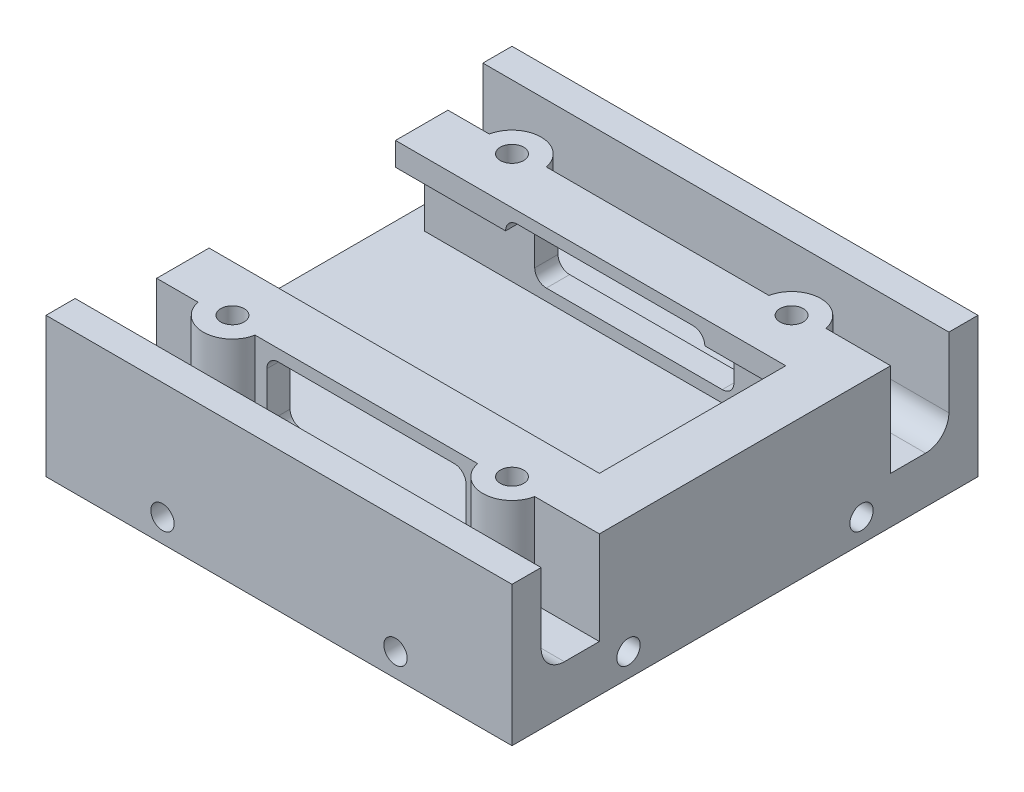
SolidWorks part; units mm, degrees
ref_plane "Front Plane" through (0, 0, 0) normal (0, 0, 1) x (1, 0, 0)
ref_plane "Top Plane" through (0, 0, 0) normal (0, 1, 0) x (1, 0, 0)
ref_plane "Right Plane" through (0, 0, 0) normal (1, 0, 0) x (0, 0, -1)
sketch "Sketch1" plane through (0, 0, 0) normal (0, 1, 0) x (1, 0, 0)
  line L1 (-20, -20) -> (20, -20)
  line L2 (-20, -20) -> (-20, 20)
  line L3 (-20, 20) -> (20, 20)
  line L4 (20, -20) -> (20, 20)
  line L5 (-20, -20) -> (20, 20) construction
  line L6 (-20, 20) -> (20, -20) construction
  point P0 (0, 0)
  dimension "D1" = 40
  dimension "D2" = 40
extrude "Boss-Extrude3" add sketch "Sketch1" along normal blind 2
sketch "Sketch5" plane through (0, 2, 0) normal (0, 1, 0) x (1, 0, 0)
  line L0 (20, -20) -> (20, 20) construction
  line L1 (-18, -10.5) -> (18, -10.5)
  line L2 (-18, -10.5) -> (-18, 10.5)
  line L3 (-18, 10.5) -> (18, 10.5)
  line L4 (18, -10.5) -> (18, 10.5)
  line L5 (-18, -10.5) -> (18, 10.5) construction
  line L6 (-18, 10.5) -> (18, -10.5) construction
  line L7 (-20, -12.5) -> (20, -12.5)
  line L8 (-20, -12.5) -> (-20, 12.5)
  line L9 (-20, 12.5) -> (20, 12.5)
  line L10 (20, -12.5) -> (20, 12.5)
  line L11 (-20, -12.5) -> (20, 12.5) construction
  line L12 (-20, 12.5) -> (20, -12.5) construction
  line L13 (-18, 10.5) -> (-18, 12.5)
  line L14 (-18, 12.5) -> (-18, -12.5)
  point P0 (0, 0)
  point P6 (0, 0)
  line M4 (20, -20) -> (20, 20)
  dimension "D1" = 36
  dimension "D2" = 21
  dimension "D3" = 25
extrude "Boss-Extrude4" add sketch "Sketch5" along normal blind 6 contours L1 L14 L7 L9 L13 L3 L4 M4 region at (0, 2, 10.9549)
sketch "Sketch6" plane through (0, 8, 0) normal (0, 1, 0) x (1, 0, 0)
  line L0 (18, -10.5) -> (18, 10.5) construction
  line L1 (-18, 12.5) -> (20, 12.5)
  line L2 (-18, 12.5) -> (-18, -12.5)
  line L3 (-18, -12.5) -> (20, -12.5)
  line L4 (20, 12.5) -> (20, -12.5)
  line L5 (-18, 10.5) -> (18, 10.5)
  line L6 (-18, 10.5) -> (-18, -10.5)
  line L7 (-18, -10.5) -> (18, -10.5)
  line L8 (18, 10.5) -> (18, -10.5)
  line L9 (18, -10.5) -> (18, 10.5) construction
  line L10 (-15.5, 8) -> (15.5, 8)
  line L11 (-12, -12) -> (12, -12)
  line L12 (-12, -12) -> (-12, 12)
  line L13 (-12, 12) -> (12, 12)
  line L14 (12, -12) -> (12, 12)
  line L15 (-12, -12) -> (12, 12) construction
  line L16 (-12, 12) -> (12, -12) construction
  line L17 (15.5, 8) -> (15.5, -8)
  line L18 (-15.5, -8) -> (15.5, -8)
  line L19 (-15.5, 8) -> (-15.5, -8)
  line L20 (-15.5, 8) -> (-18, 8)
  line L21 (-15.5, -8) -> (-18, -8)
  circle A0 centre (-12, 12) radius 2.5
  circle A1 centre (12, 12) radius 2.5
  circle A2 centre (-12, -12) radius 2.5
  circle A3 centre (12, -12) radius 2.5
  point P15 (0, 0)
  line M14 (18, -10.5) -> (-18, -10.5)
  line M15 (-18, -10.5) -> (-18, -12.5)
  line M16 (-18, -12.5) -> (20, -12.5)
  line M17 (20, -12.5) -> (20, 12.5)
  line M18 (20, 12.5) -> (-18, 12.5)
  line M19 (-18, 12.5) -> (-18, 10.5)
  line M20 (-18, 10.5) -> (18, 10.5)
  line M21 (18, 10.5) -> (18, -10.5)
  dimension "D3" = 2.5
  dimension "D1" = 24
  dimension "D2" = 24
extrude "Boss-Extrude5" add sketch "Sketch6" along normal blind 2 contours A2 M14 M15 M16 | L3 A2 L11 L12 L7 | L11 A2 L12 M14 | A3 A2 L11 M14 | A3 L11 A2 M16 | A3 A1 L5 M16 M17 M18 M21 M14 | A1 L13 A0 M20 | A1 A0 L13 M18 | A0 M18 M19 M20 | A2 | A3 | A1 | A0 region at (-16.1854, 8, -11.4801) region at (0, 8, -12.2502) region at (0, 8, -11.2437) region at (18.3674, 8, 0) region at (-16.1854, 8, 11.4801) region at (-12.6882, 8, 11.6792) region at (-10.8251, 8, 11.2761) region at (0, 8, 11.2437) region at (0, 8, 12.2502)
extrude "Boss-Extrude6" add sketch "Sketch6<3>" against normal blind 6 contours L1 A0 | L1 A1 | L3 A2 | L3 A3 region at (-12, 8, -13.3359) region at (12, 8, -13.3359) region at (-12, 8, 13.3359) region at (12, 8, 13.3359)
sketch "Sketch6<3>" plane through (0, 8, 0) normal (0, 1, 0) x (1, 0, 0) same geometry as "Sketch6"
extrude "Boss-Extrude7" add sketch "Sketch6<4>" along normal blind 2 contours A2 L12 L18 L21 L2 M14 | A3 L14 L18 L12 A2 M14 | A3 L5 A1 L14 L10 L17 L18 M14 M21 | A1 A0 L12 L10 L14 M20 | A0 L2 L20 L10 L12 M20 region at (-15.2286, 8, -9.1634) region at (0, 8, -9.2088) region at (-15.2286, 8, 9.1634) region at (16.1342, 8, 0) region at (0, 8, 9.2088)
sketch "Sketch6<4>" plane through (0, 8, 0) normal (0, 1, 0) x (1, 0, 0) same geometry as "Sketch6"
sketch "Sketch7" plane through (0, 10, 0) normal (0, 1, 0) x (1, 0, 0)
  circle A1 centre (-12, 12) radius 1
  circle A2 centre (12, 12) radius 1
  circle A3 centre (12, -12) radius 1
  circle A4 centre (-12, -12) radius 1
  dimension "D1" = 2
  dimension "D2" = 2
extrude "Cut-Extrude1" cut sketch "Sketch7" against normal blind 5
sketch "Sketch8" plane through (0, 0, 12.5) normal (0, 0, 1) x (1, 0, 0)
  line L0 (9.5505, 10) -> (9.5505, 2) construction
  line L1 (-9.5505, 10) -> (9.5505, 10)
  line L2 (-9.5505, 10) -> (-9.5505, 2)
  line L3 (-9.5505, 2) -> (9.5505, 2)
  line L4 (9.5505, 10) -> (9.5505, 2)
  line L5 (-20, 2) -> (20, 2) construction
  line L6 (-8.5505, 8) -> (-8.5505, 4)
  line L7 (-7.5505, 3) -> (7.5505, 3)
  line L8 (8.5505, 8) -> (8.5505, 4)
  line L9 (-7.5505, 9) -> (7.5505, 9)
  line L10 (-8.5505, 3) -> (8.5505, 3) construction
  line L11 (-8.5505, 9) -> (-8.5505, 3) construction
  line L12 (8.5505, 9) -> (8.5505, 3) construction
  line L13 (-8.5505, 9) -> (8.5505, 9) construction
  arc A0 (-7.5505, 3) -> (-8.5505, 4) centre (-7.5505, 4) cw
  arc A1 (8.5505, 4) -> (7.5505, 3) centre (7.5505, 4) cw
  arc A2 (7.5505, 9) -> (8.5505, 8) centre (7.5505, 8) cw
  arc A3 (-8.5505, 8) -> (-7.5505, 9) centre (-7.5505, 8) cw
  dimension "D2" = 1
  dimension "D1" = 1
extrude "Cut-Extrude2" cut sketch "Sketch8" against normal blind 34 contours A3 L6 A0 L7 A1 L8 A2 L9 region at (0, 6, 12.5)
sketch "Sketch9" plane through (0, 2, 0) normal (0, 1, 0) x (1, 0, 0)
  line L0 (-20, 17.5) -> (20, 17.5)
  line L1 (-20, 20) -> (20, 20)
  line L2 (-20, 20) -> (-20, -20)
  line L3 (-20, -20) -> (20, -20)
  line L4 (20, 20) -> (20, -20)
  line L5 (-17.5, -17.5) -> (17.5, -17.5)
  line L6 (-17.5, -17.5) -> (-17.5, 17.5)
  line L7 (-17.5, 17.5) -> (17.5, 17.5)
  line L8 (17.5, -17.5) -> (17.5, 17.5)
  line L9 (-17.5, -17.5) -> (17.5, 17.5) construction
  line L10 (-17.5, 17.5) -> (17.5, -17.5) construction
  line L11 (-20, -17.5) -> (20, -17.5)
  point P6 (0, 0)
  line M12 (20, 12.5) -> (20, 20)
  line M13 (20, 20) -> (-20, 20)
  line M14 (-20, 20) -> (-20, -20)
  line M15 (-20, -20) -> (20, -20)
  line M16 (20, -20) -> (20, -12.5)
  dimension "D1" = 35
  dimension "D2" = 35
extrude "Boss-Extrude8" add sketch "Sketch9" along normal blind 8 contours L0 M14 M12 M13 | L11 L2 L5 M15 M16 region at (0, 2, -18.75) region at (0, 2, 18.75)
sketch "Sketch10" plane through (-20, 0, 0) normal (-1, 0, 0) x (0, 0, 1)
  line L0 (-12.5, 10) -> (-14.5, 10) construction
  line L1 (-15.5, 2) -> (-14.5, 2)
  line L2 (-17.5, 4) -> (-17.5, 10)
  line L3 (-17.5, 10) -> (-14.5, 10)
  line L4 (-14.5, 2) -> (-14.5, 10)
  line L5 (0, 0) -> (0, 6.4632)
  line L6 (-20, 0) -> (20, 0) construction
  arc A0 (-15.5, 2) -> (-17.5, 4) centre (-15.5, 4) cw
  arc A1 (15.5, 2) -> (17.5, 4) centre (15.5, 4) ccw
  point P9 (-17.5, 2)
  line M10 (17.5, 10) -> (17.5, 2)
  line M11 (17.5, 2) -> (-17.5, 2)
  line M12 (-17.5, 2) -> (-17.5, 10)
  dimension "D1" = 2
extrude "Boss-Extrude9" add sketch "Sketch10" against normal up to surface (40 mm away) contours A0 M11 M12 | A1 M11 M10 region at (-20, 2.4467, -17.0533) region at (-20, 2.4467, 17.0533) up to face at (20, 5.6667, 0)
sketch "Sketch11" plane through (0, 0, 0) normal (0, -1, 0) x (1, 0, 0)
  line L1 (-20, -20) -> (20, -20)
  line L2 (-20, -20) -> (-20, 20)
  line L3 (-20, 20) -> (20, 20)
  line L4 (20, -20) -> (20, 20)
  line L5 (-20, -20) -> (20, 20) construction
  line L6 (-20, 20) -> (20, -20) construction
  point P0 (0, 0)
extrude "Boss-Extrude10" add sketch "Sketch11" along normal blind 2
sketch "Sketch13" plane through (20, 0, 0) normal (1, 0, 0) x (0, 0, -1)
  circle A0 centre (-10, 0) radius 1
  circle A1 centre (10, 0) radius 1
extrude "Cut-Extrude3" cut sketch "Sketch13" against normal blind 5
pattern_circular "CirPattern1" count 4 every 90 about axis through (0, -2, 0) along (0, -1, 0) of "Cut-Extrude3"
